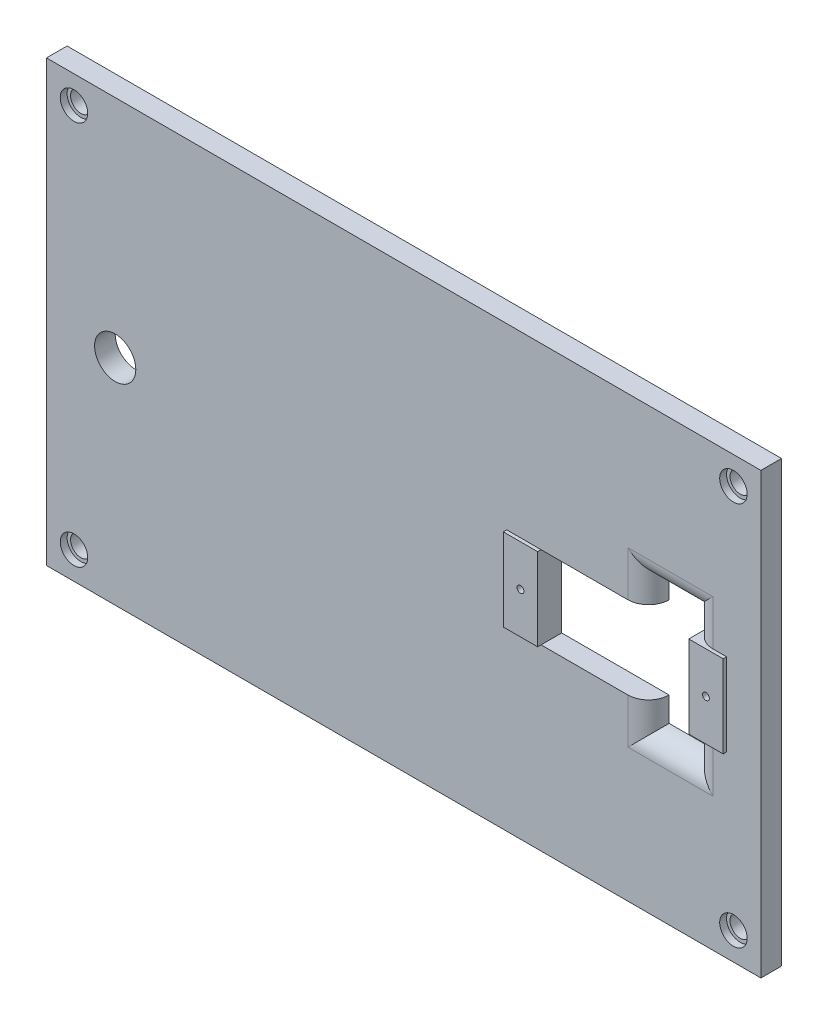
SolidWorks part; units mm, degrees
ref_plane "前视基准面" through (0, 0, 0) normal (0, 0, 1) x (1, 0, 0)
ref_plane "上视基准面" through (0, 0, 0) normal (0, 1, 0) x (1, 0, 0)
ref_plane "右视基准面" through (0, 0, 0) normal (1, 0, 0) x (0, 0, -1)
sketch "草图1" plane through (0, 0, 0) normal (0, 0, 1) x (1, 0, 0)
  line L1 (52, -32) -> (-52, -32)
  line L2 (52, -32) -> (52, 32)
  line L3 (52, 32) -> (-52, 32)
  line L4 (-52, -32) -> (-52, 32)
  line L5 (52, -32) -> (-52, 32) construction
  line L6 (52, 32) -> (-52, -32) construction
  point P0 (0, 0)
  dimension "D1" = 64
  dimension "D2" = 104
extrude "凸台-拉伸1" add sketch "草图1" along normal blind 3
sketch "草图2" plane through (0, 0, 3) normal (0, 0, 1) x (1, 0, 0)
  line L2 (0, 0) -> (0, 50000) construction
  line L3 (0, 0) -> (-50000, 0) construction
  circle A1 centre (-48, 28) radius 1.5
  circle A2 centre (48, 28) radius 1.5
  circle A3 centre (48, -28) radius 1.5
  circle A4 centre (-48, -28) radius 1.5
  dimension "D3" = 3
extrude "切除-拉伸1" cut sketch "草图2" against normal through all
sketch "草图4" plane through (0, 0, 3) normal (0, 0, 1) x (1, 0, 0)
  line L0 (0, 0) -> (0, 50000) construction
  line L1 (0, 0) -> (50000, 0) construction
  circle A0 centre (48, 28) radius 2
  circle A1 centre (-48, 28) radius 2
  circle A2 centre (-48, -28) radius 2
  circle A3 centre (48, -28) radius 2
  dimension "D1" = 4
extrude "切除-拉伸3" cut sketch "草图4" against normal blind 1
sketch "草图12" plane through (0, 0, 3) normal (0, 0, 1) x (1, 0, 0)
  line L0 (0, 0) -> (-50000, 0) construction
  line L2 (15, -6) -> (20, -6)
  line L3 (15, -6) -> (15, 6)
  line L4 (15, 6) -> (20, 6)
  line L5 (20, -6) -> (20, 6)
  line L6 (15, -6) -> (20, 6) construction
  line L7 (15, 6) -> (20, -6) construction
  line L8 (42, -6) -> (47, -6)
  line L9 (42, -6) -> (42, 6)
  line L10 (42, 6) -> (47, 6)
  line L11 (47, -6) -> (47, 6)
  line L12 (42, -6) -> (47, 6) construction
  line L13 (42, 6) -> (47, -6) construction
  line L14 (52, -32) -> (52, 32) construction
  point P3 (17.5, 0)
  point P8 (44.5, 0)
  dimension "D1" = 12
  dimension "D2" = 5
  dimension "D3" = 12
  dimension "D4" = 5
  dimension "D5" = 22
  dimension "D6" = 5
extrude "凸台-拉伸4" add sketch "草图12" along normal blind 0.5
sketch "草图13" plane through (0, 0, 3.5) normal (0, 0, 1) x (1, 0, 0)
  line L0 (20, -6) -> (20, 6) construction
  line L1 (42, 6) -> (42, -6) construction
  circle A0 centre (17.5, 0) radius 0.5
  circle A1 centre (44.5, 0) radius 0.5
  dimension "D1" = 2.5
  dimension "D2" = 2.5
  dimension "D3" = 1
extrude "切除-拉伸8" cut sketch "草图13" against normal through all
sketch "草图15" plane through (0, 0, 3) normal (0, 0, 1) x (1, 0, 0)
  line L1 (20, 6) -> (42, 6)
  line L2 (20, 6) -> (20, -6)
  line L3 (20, -6) -> (42, -6)
  line L4 (42, 6) -> (42, -6)
  dimension "D1" = 12
  dimension "D2" = 22
extrude "切除-拉伸10" cut sketch "草图15" against normal through all
sketch "草图17" plane through (0, 0, 3) normal (0, 0, 1) x (1, 0, 0)
  line L0 (42, 6) -> (42, -6) construction
  line L1 (42, -9.5801) -> (35.6418, -9.5801)
  line L2 (42, -9.5801) -> (42, 9.5801)
  line L3 (42, 9.5801) -> (35.6418, 9.5801)
  line L4 (35.6418, -9.5801) -> (35.6418, 9.5801)
  line L5 (42, -9.5801) -> (35.6418, 9.5801) construction
  line L6 (42, 9.5801) -> (35.6418, -9.5801) construction
  line L9 (17.5, 0) -> (50017.5, 0) construction
  point P0 (3.8219, 10.1918)
  point P5 (38.8209, 0)
  dimension "D1" = 19.1603
  dimension "D2" = 6.3582
  dimension "D3" = 0
extrude "切除-拉伸11" cut sketch "草图17" against normal blind 4
fillet "圆角2" radius 3 6 edges at (35.6418, -7.7901, 3) (38.8209, -9.5801, 3) (42, -7.7901, 3) (42, 7.7901, 3) (38.8209, 9.5801, 3) (35.6418, 7.7901, 3)
sketch "草图18" plane through (0, 0, 3) normal (0, 0, 1) x (1, 0, 0)
  line L0 (-52, 32) -> (-52, -32) construction
  circle A0 centre (-42, -0.8) radius 3
  dimension "D1" = 6
  dimension "D2" = 10
extrude "切除-拉伸12" cut sketch "草图18" against normal blind 6
sketch "草图19" plane through (0, 0, 3) normal (0, 0, 1) x (1, 0, 0)
  line L0 (-42, -0.8) -> (49956.1893, 424.7243) construction
  line L1 (52, -32) -> (52, 32) construction
  point P5 (52, 0)
